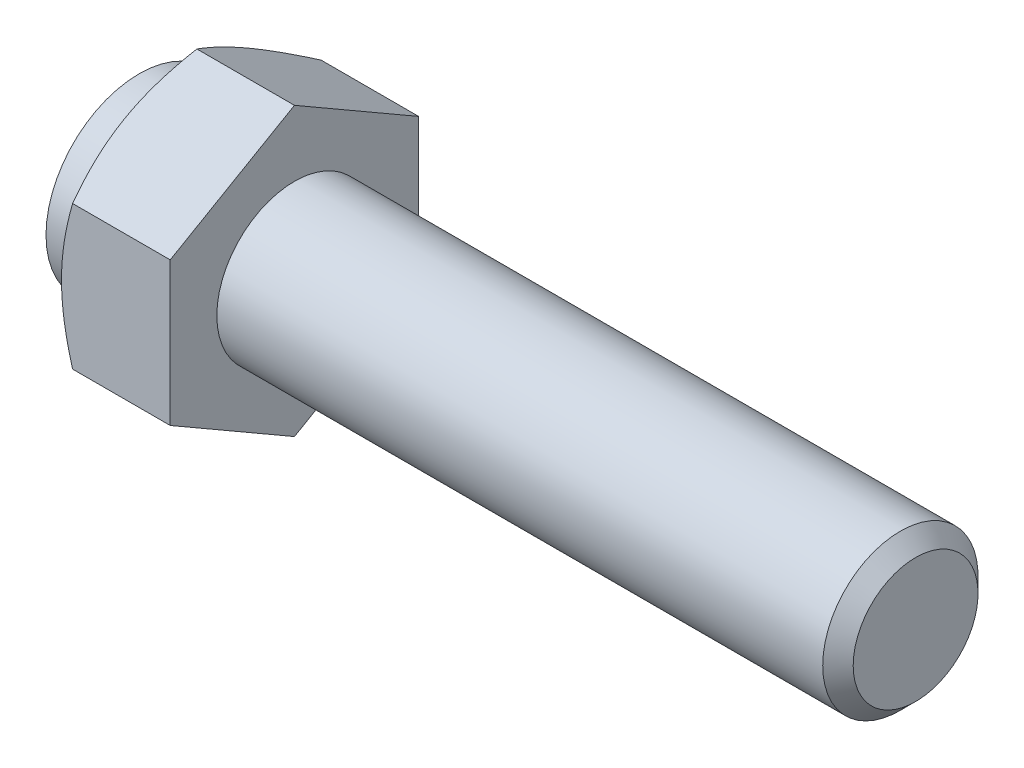
SolidWorks part; units mm, degrees
ref_plane "前视基准面" through (0, 0, 0) normal (0, 0, 1) x (1, 0, 0)
ref_plane "上视基准面" through (0, 0, 0) normal (0, 1, 0) x (1, 0, 0)
ref_plane "右视基准面" through (0, 0, 0) normal (1, 0, 0) x (0, 0, -1)
sketch "草图1" plane through (0, 0, 0) normal (0, 0, 1) x (1, 0, 0)
  line L0 (-5, 0) -> (-5, 3)
  line L1 (-5, 3) -> (-3.5, 3)
  line L2 (-3.5, 3) -> (-3.5, 4)
  line L3 (-3.5, 4) -> (-3.0381, 4.8)
  line L4 (-3.0381, 4.8) -> (0, 4.8)
  line L5 (0, 4.8) -> (0, 2.5)
  line L6 (0, 2.5) -> (19.5095, 2.5)
  line L7 (19.5095, 2.5) -> (20, 2.0095)
  line L8 (20, 2.0095) -> (20, 0)
  line L9 (20, 0) -> (-5, 0)
  line L10 (20, 0) -> (-5, 0) construction
revolve "旋转1" add sketch "草图1" angle 360 about L10 reverse direction yes
cosmetic thread "装饰螺纹线1"
ref_plane "基准面1" through (10, 0, 0) normal (1, 0, 0) x (0, 0, -1)
ref_plane "基准面2" through (20, 0, 0) normal (1, 0, 0) x (0, 0, -1)
sketch "草图2" plane through (0, 0, 0) normal (1, 0, 0) x (0, 0, -1)
  line L0 (-9.2, -9.2) -> (9.2, -9.2)
  line L1 (9.2, -9.2) -> (9.2, 9.2)
  line L2 (9.2, 9.2) -> (-9.2, 9.2)
  line L3 (-9.2, 9.2) -> (-9.2, -9.2)
  line L4 (-4, 2.3094) -> (-4, -2.3094)
  line L5 (-4, -2.3094) -> (0, -4.6188)
  line L6 (0, -4.6188) -> (4, -2.3094)
  line L7 (4, -2.3094) -> (4, 2.3094)
  line L8 (4, 2.3094) -> (0, 4.6188)
  line L9 (0, 4.6188) -> (-4, 2.3094)
extrude "切除-拉伸1" cut sketch "草图2" against normal blind 5
ref_plane "基准面3" through (-5, 0, 0) normal (1, 0, 0) x (0, 0, -1)
ref_plane "ustb_n XY" through (10, 0, 0) normal (1, 0, 0) x (0, 0, -1)
ref_plane "ustb_n XZ" through (0, 0, 0) normal (0, -1, 0) x (1, 0, 0)
ref_plane "ustb_n YZ" through (0, 0, 0) normal (0, 0, -1) x (-1, 0, 0)
ref_axis "ustb_n X" through (10, 0, 80.9) along (0, 0, -1)
ref_axis "ustb_n Y" through (10, -50, 0) along (0, 1, 0)
ref_axis "ustb_n Z" through (80.9, 0, 0) along (-1, 0, 0)
sketch3d "ustb_n"
  point P0 (10, 0, 0)
ref_plane "cp XY" through (-5, 0, 0) normal (1, 0, 0) x (0, 0, -1)
ref_plane "cp XZ" through (0, 0, 0) normal (0, -1, 0) x (1, 0, 0)
ref_plane "cp YZ" through (0, 0, 0) normal (0, 0, -1) x (-1, 0, 0)
ref_axis "cp X" through (-5, 0, 80.9) along (0, 0, -1)
ref_axis "cp Y" through (-5, -50, 0) along (0, 1, 0)
ref_axis "cp Z" through (80.9, 0, 0) along (-1, 0, 0)
sketch3d "cp"
  point P0 (-5, 0, 0)
